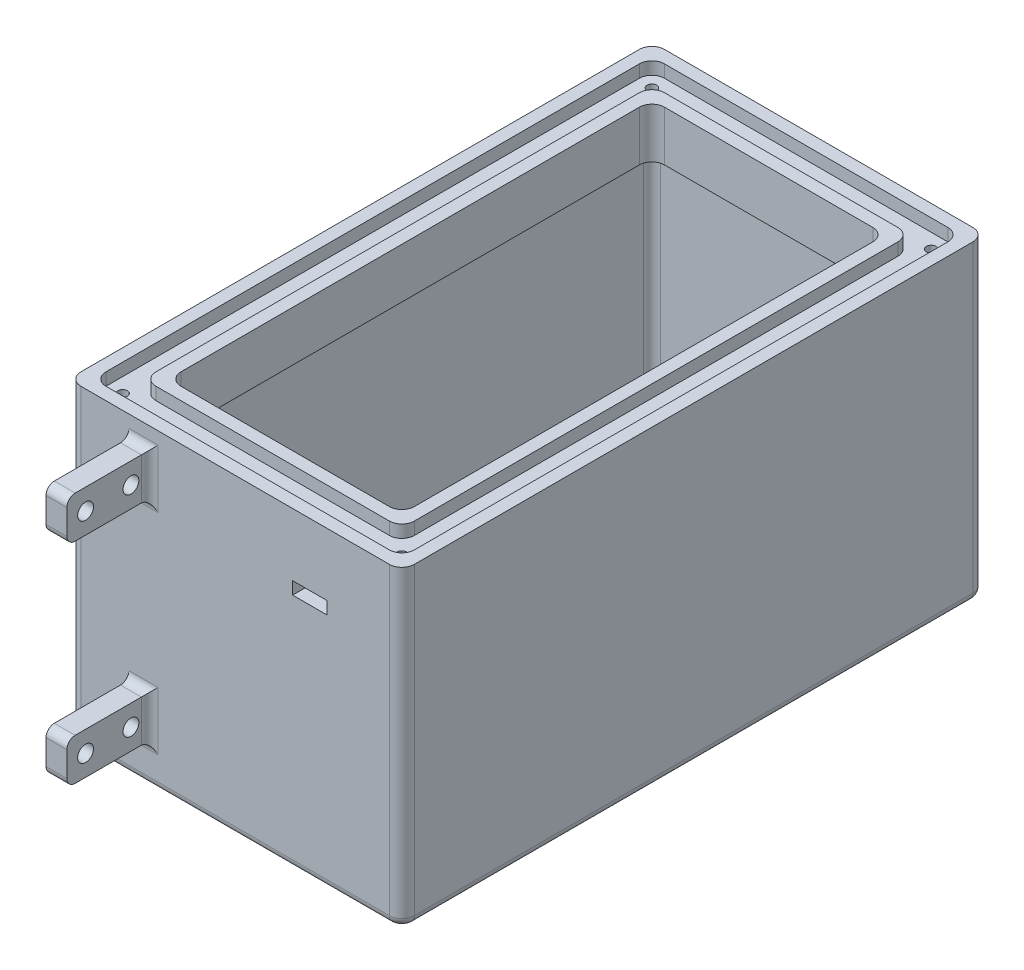
SolidWorks part; units mm, degrees
material "ABS"
ref_plane "Front Plane" through (0, 0, 0) normal (0, 0, 1) x (1, 0, 0)
ref_plane "Top Plane" through (0, 0, 0) normal (0, 1, 0) x (1, 0, 0)
ref_plane "Right Plane" through (0, 0, 0) normal (1, 0, 0) x (0, 0, -1)
sketch "Sketch1" plane through (0, 0, 0) normal (0, 1, 0) x (1, 0, 0)
  line L1 (0, 0) -> (80, 0)
  line L2 (0, 0) -> (0, 140)
  line L3 (0, 140) -> (80, 140)
  line L4 (80, 0) -> (80, 140)
  dimension "D1" = 140
  dimension "D2" = 80
extrude "Boss-Extrude1" add sketch "Sketch1" along normal blind 3
sketch "Sketch2" plane through (0, 3, 0) normal (0, 1, 0) x (1, 0, 0)
  line L1 (0, 140) -> (80, 140)
  line L2 (0, 140) -> (0, 0)
  line L3 (0, 0) -> (80, 0)
  line L4 (80, 140) -> (80, 0)
  line L5 (3, 137) -> (77, 137)
  line L6 (3, 137) -> (3, 3)
  line L7 (3, 3) -> (77, 3)
  line L8 (77, 137) -> (77, 3)
  dimension "D1" = 3
  dimension "D2" = 3
  dimension "D3" = 3
  dimension "D4" = 3
extrude "Boss-Extrude2" add sketch "Sketch2" along normal blind 60
fillet "Fillet1" radius 2 8 edges at (40, 3, -3) (77, 3, -70) (3, 3, -70) (40, 3, -137) (77, 33, -3) (3, 33, -3) (77, 33, -137) (3, 33, -137)
fillet "Fillet2" radius 2 4 edges at (40, 0, -140) (0, 0, -70) (40, 0, 0) (80, 0, -70)
sketch "Sketch6" plane through (0, 63, 0) normal (0, 1, 0) x (1, 0, 0)
  line L1 (0, 140) -> (80, 140)
  line L2 (0, 140) -> (0, 0)
  line L3 (0, 0) -> (80, 0)
  line L4 (80, 140) -> (80, 0)
  line L5 (15, 128) -> (65, 128)
  line L6 (12, 125) -> (12, 15)
  line L7 (15, 12) -> (65, 12)
  line L8 (68, 125) -> (68, 15)
  arc A0 (65, 12) -> (68, 15) centre (65, 15) ccw
  arc A1 (12, 15) -> (15, 12) centre (15, 15) ccw
  arc A2 (65, 128) -> (68, 125) centre (65, 125) cw
  arc A3 (15, 128) -> (12, 125) centre (15, 125) ccw
  dimension "D5" = 3
  dimension "D1" = 12
  dimension "D2" = 12
  dimension "D3" = 12
  dimension "D4" = 12
extrude "Boss-Extrude3" add sketch "Sketch6" along normal blind 12
sketch "Sketch7" plane through (0, 75, 0) normal (0, 1, 0) x (1, 0, 0)
  line L0 (80, 140) -> (0, 140) construction
  line L1 (6, 137) -> (74, 137)
  line L2 (3, 134) -> (3, 6)
  line L3 (6, 3) -> (74, 3)
  line L4 (77, 134) -> (77, 6)
  line L5 (80, 0) -> (80, 140) construction
  line L6 (0, 0) -> (80, 0) construction
  line L7 (0, 140) -> (0, 0) construction
  line L13 (12, 131) -> (68, 131)
  line L14 (9, 128) -> (9, 12)
  line L15 (12, 9) -> (68, 9)
  line L16 (71, 128) -> (71, 12)
  arc A0 (3, 6) -> (6, 3) centre (6, 6) ccw
  arc A1 (74, 3) -> (77, 6) centre (74, 6) ccw
  arc A2 (74, 137) -> (77, 134) centre (74, 134) cw
  arc A3 (6, 137) -> (3, 134) centre (6, 134) ccw
  arc A7 (9, 12) -> (12, 9) centre (12, 12) ccw
  arc A8 (68, 9) -> (71, 12) centre (68, 12) ccw
  arc A9 (68, 131) -> (71, 128) centre (68, 128) cw
  arc A10 (12, 131) -> (9, 128) centre (12, 128) ccw
  dimension "D5" = 3
  dimension "D6" = 6
  dimension "D10" = 3
  dimension "D1" = 3
  dimension "D2" = 3
  dimension "D3" = 3
  dimension "D4" = 3
  dimension "D7" = 6
  dimension "D8" = 6
  dimension "D9" = 6
extrude "Cut-Extrude1" cut sketch "Sketch7" against normal blind 3
sketch "Sketch8" plane through (0, 72, 0) normal (0, 1, 0) x (1, 0, 0)
  line L0 (0, 0) -> (80, 0) construction
  line L1 (0, 140) -> (0, 0) construction
  line L2 (80, 0) -> (80, 140) construction
  line L3 (80, 140) -> (0, 140) construction
  circle A0 centre (6.5, 6.5) radius 1.15
  circle A1 centre (73.5, 6.5) radius 1.15
  circle A2 centre (73.5, 133.5) radius 1.15
  circle A3 centre (6.5, 133.5) radius 1.15
  dimension "D1" = 2.3
  dimension "D2" = 2.3
  dimension "D3" = 2.3
  dimension "D4" = 2.3
  dimension "D5" = 6.5
  dimension "D6" = 6.5
  dimension "D7" = 6.5
  dimension "D8" = 6.5
  dimension "D9" = 6.5
  dimension "D10" = 6.5
  dimension "D11" = 6.5
  dimension "D12" = 6.5
extrude "Cut-Extrude2" cut sketch "Sketch8" against normal blind 6
fillet "Fillet3" radius 3 8 edges at (0.5858, 0.5858, -139.4142) (79.4142, 0.5858, -139.4142) (79.4142, 0.5858, -0.5858) (0.5858, 0.5858, -0.5858) (0, 38.5, -140) (80, 38.5, -140) (80, 38.5, 0) (0, 38.5, 0)
sketch "Sketch9" plane through (0, 0, 0) normal (-1, 0, 0) x (0, 0, 1)
  line L0 (-137, 75) -> (-3, 75) construction
  line L1 (-87, 55) -> (-82, 55)
  line L2 (-87, 55) -> (-87, 25)
  line L3 (-87, 25) -> (-82, 25)
  line L4 (-82, 55) -> (-82, 25)
  line L6 (-140, 2) -> (-140, 75) construction
  line L7 (0, 75) -> (0, 2) construction
  dimension "D1" = 30
  dimension "D2" = 5
  dimension "D3" = 20
  dimension "D4" = 53
  dimension "D5" = 82
extrude "Boss-Extrude4" add sketch "Sketch9" along normal blind 15
sketch "Sketch10" plane through (0, 0, -87) normal (0, 0, -1) x (-1, 0, 0)
  line L0 (15, 25) -> (0, 25) construction
  line L1 (15, 55) -> (10, 55)
  line L2 (15, 55) -> (15, 25)
  line L3 (15, 25) -> (10, 25)
  line L4 (10, 55) -> (10, 25)
  dimension "D1" = 5
extrude "Boss-Extrude5" add sketch "Sketch10" along normal blind 53
fillet "Fillet4" radius 3 4 edges at (0, 25, -84.5) (0, 55, -84.5) (0, 40, -87) (0, 40, -82)
fillet "Fillet5" radius 3 4 edges at (-12.5, 25, -140) (-12.5, 55, -140) (-10, 40, -87) (-15, 40, -82)
sketch "Sketch12" plane through (0, 0, 0) normal (0, 0, 1) x (1, 0, 0)
  line L0 (0, 2) -> (0, 75) construction
  line L1 (14.5, 70) -> (19.5, 70)
  line L2 (14.5, 70) -> (14.5, 60)
  line L3 (14.5, 60) -> (19.5, 60)
  line L4 (19.5, 70) -> (19.5, 60)
  line L5 (14.5, 19.67) -> (19.5, 19.67)
  line L6 (14.5, 19.67) -> (14.5, 9.67)
  line L7 (14.5, 9.67) -> (19.5, 9.67)
  line L8 (19.5, 19.67) -> (19.5, 9.67)
  line L9 (3, 75) -> (77, 75) construction
  dimension "D1" = 5
  dimension "D2" = 10
  dimension "D3" = 5
  dimension "D4" = 10
  dimension "D5" = 40.33
  dimension "D6" = 14.5
  dimension "D7" = 5
extrude "Boss-Extrude6" add sketch "Sketch12" along normal blind 19.88
fillet "Fillet6" radius 2 6 edges at (17, 19.67, 0) (17, 9.67, 0) (19.5, 14.67, 0) (19.5, 65, 0) (17, 60, 0) (17, 70, 0)
fillet "Fillet7" radius 2 4 edges at (17, 9.67, 19.88) (17, 19.67, 19.88) (17, 60, 19.88) (17, 70, 19.88)
sketch "Sketch13" plane through (14.5, 0, 0) normal (-1, 0, 0) x (0, 0, 1)
  line L0 (0, 65) -> (19.88, 65) construction
  line L2 (19.88, 68) -> (19.88, 62) construction
  line L3 (0, 14.67) -> (19.88, 14.67) construction
  line L5 (19.88, 17.67) -> (19.88, 11.67) construction
  line L6 (0, 21.67) -> (0, 7.67) construction
  line L7 (0, 72) -> (0, 58) construction
  circle A0 centre (4.5, 65) radius 1.9
  circle A1 centre (15.38, 65) radius 1.9
  circle A2 centre (4.5, 14.67) radius 1.9
  circle A3 centre (15.38, 14.67) radius 1.9
  dimension "D1" = 3.8
  dimension "D2" = 3.8
  dimension "D3" = 3.8
  dimension "D4" = 3.8
  dimension "D5" = 4.5
  dimension "D6" = 4.5
  dimension "D7" = 4.5
  dimension "D8" = 4.5
extrude "Cut-Extrude3" cut sketch "Sketch13" against normal through all
sketch "Sketch14" plane through (0, 0, 0) normal (0, 0, 1) x (1, 0, 0)
  line L0 (3, 75) -> (77, 75) construction
  line L1 (53.8, 60) -> (62, 60)
  line L2 (53.8, 60) -> (53.8, 57)
  line L3 (53.8, 57) -> (62, 57)
  line L4 (62, 60) -> (62, 57)
  line L5 (77, 2) -> (77, 75) construction
  dimension "D1" = 8.2
  dimension "D2" = 3
  dimension "D3" = 15
  dimension "D4" = 15
extrude "Cut-Extrude4" cut sketch "Sketch14" against normal blind 3
sketch "Sketch15" plane through (0, 0, 0) normal (0, -1, 0) x (1, 0, 0)
  line L0 (0, -70) -> (80, -70) construction
  line L1 (0, -137) -> (0, -3) construction
  line L2 (80, -3) -> (80, -137) construction
  line L3 (40, 0) -> (40, -140) construction
  line L4 (3, 0) -> (77, 0) construction
  line L5 (77, -140) -> (3, -140) construction
  line L7 (21.25, -44.75) -> (58.75, -44.75)
  line L8 (19.75, -46.25) -> (19.75, -93.75)
  line L9 (21.25, -95.25) -> (58.75, -95.25)
  line L10 (60.25, -46.25) -> (60.25, -93.75)
  line L11 (19.75, -44.75) -> (60.25, -95.25) construction
  line L12 (19.75, -95.25) -> (60.25, -44.75) construction
  line L13 (19.25, -42.75) -> (60.75, -42.75)
  line L14 (17.75, -44.25) -> (17.75, -95.75)
  line L15 (19.25, -97.25) -> (60.75, -97.25)
  line L16 (62.25, -44.25) -> (62.25, -95.75)
  line L17 (17.75, -42.75) -> (62.25, -97.25) construction
  line L18 (17.75, -97.25) -> (62.25, -42.75) construction
  arc A0 (19.75, -93.75) -> (21.25, -95.25) centre (21.25, -93.75) ccw
  arc A1 (17.75, -95.75) -> (19.25, -97.25) centre (19.25, -95.75) ccw
  arc A2 (58.75, -95.25) -> (60.25, -93.75) centre (58.75, -93.75) ccw
  arc A3 (60.75, -97.25) -> (62.25, -95.75) centre (60.75, -95.75) ccw
  arc A4 (58.75, -44.75) -> (60.25, -46.25) centre (58.75, -46.25) cw
  arc A5 (60.75, -42.75) -> (62.25, -44.25) centre (60.75, -44.25) cw
  arc A6 (21.25, -44.75) -> (19.75, -46.25) centre (21.25, -46.25) ccw
  arc A7 (19.25, -42.75) -> (17.75, -44.25) centre (19.25, -44.25) ccw
  point P12 (40, -70)
  point P17 (40, -70)
  dimension "D5" = 1.5
  dimension "D1" = 40.5
  dimension "D2" = 50.5
  dimension "D3" = 2
  dimension "D4" = 2
extrude "Boss-Extrude7" add sketch "Sketch15" along normal blind 1.35
sketch "Sketch16" plane through (0, 0, 0) normal (0, -1, 0) x (1, 0, 0)
  line L0 (40, -44.75) -> (40, -95.25) construction
  line L1 (58.75, -44.75) -> (21.25, -44.75) construction
  line L2 (21.25, -95.25) -> (58.75, -95.25) construction
  line L4 (37.5, -46.68) -> (42.5, -46.68)
  line L5 (37.5, -46.68) -> (37.5, -49.38)
  line L6 (37.5, -49.38) -> (42.5, -49.38)
  line L7 (42.5, -46.68) -> (42.5, -49.38)
  line L8 (37.5, -46.68) -> (42.5, -49.38) construction
  line L9 (37.5, -49.38) -> (42.5, -46.68) construction
  point P6 (40, -48.03)
  dimension "D1" = 5
  dimension "D2" = 2.7
  dimension "D3" = 1.93
extrude "Cut-Extrude5" cut sketch "Sketch16" against normal blind 3
